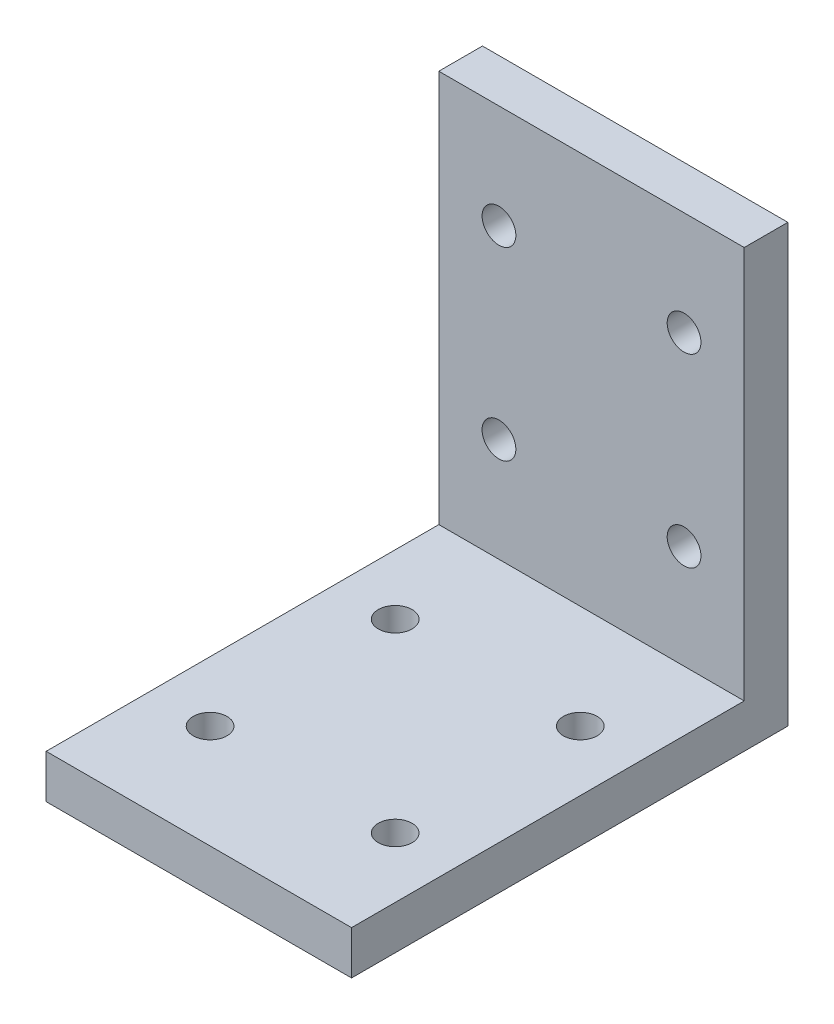
SolidWorks part; units mm, degrees
ref_plane "Front Plane" through (0, 0, 0) normal (0, 0, 1) x (1, 0, 0)
ref_plane "Top Plane" through (0, 0, 0) normal (0, 1, 0) x (1, 0, 0)
ref_plane "Right Plane" through (0, 0, 0) normal (1, 0, 0) x (0, 0, -1)
sketch "Sketch1" plane through (0, 0, 0) normal (1, 0, 0) x (0, 0, -1)
  line L0 (0, 0) -> (63.5, 0)
  line L1 (63.5, 0) -> (63.5, 63.5)
  line L2 (63.5, 63.5) -> (57.15, 63.5)
  line L3 (57.15, 63.5) -> (57.15, 6.35)
  line L4 (57.15, 6.35) -> (0, 6.35)
  line L5 (0, 6.35) -> (0, 0)
  dimension "D1" = 63.5
  dimension "D2" = 6.35
  dimension "D3" = 6.35
extrude "Boss-Extrude1" add sketch "Sketch1" against normal mid plane 44.45
hole_wizard "#10 (0.1935) Diameter Hole1" positions "Sketch4" profile "Sketch3" hole size "#10" standard "ANSI Inch" end condition up to next
sketch "Sketch4" plane through (0, 6.35, 0) normal (0, 1, 0) x (1, 0, 0)
  line L1 (-13.4704, 42.0454) -> (13.4704, 42.0454) construction
  line L2 (-13.4704, 42.0454) -> (-13.4704, 15.1046) construction
  line L3 (-13.4704, 15.1046) -> (13.4704, 15.1046) construction
  line L4 (13.4704, 42.0454) -> (13.4704, 15.1046) construction
  line L5 (-13.4704, 42.0454) -> (13.4704, 15.1046) construction
  line L6 (-13.4704, 15.1046) -> (13.4704, 42.0454) construction
  line L7 (22.225, 57.15) -> (22.225, 0) construction
  line L9 (-22.225, 28.575) -> (22.225, 28.575) construction
  line L10 (-22.225, 57.15) -> (-22.225, 0) construction
  point P2 (13.4704, 15.1046)
  point P73 (-13.4704, 42.0454)
  point P74 (-13.4704, 15.1046)
  point P75 (13.4704, 42.0454)
  point P85 (0, 28.575)
  point P92 (0, 28.575)
  dimension "D1" = 38.1
sketch "Sketch3" plane through (13.4704, 6.35, -15.1046) normal (1, 0, 0) x (0, 0, 1)
  line L0 (0, 0) -> (0, 6.351)
  line L1 (0, 6.351) -> (2.4574, 6.351)
  line L2 (2.4574, 6.351) -> (2.4574, 0)
  line L5 (2.4574, 0) -> (0, 0)
  line L11 (0, -6.35) -> (0, 107.95) construction
  dimension "Thru Hole Dia." = 4.9149
  dimension "Thru Hole Depth" = 6.351
ref_plane "Plane1" through (0, 31.75, -31.75) normal (0, 0.7071, -0.7071) x (-1, 0, 0)
mirror "Mirror1" about plane through (0, 31.75, -31.75) normal (0, 0.7071, -0.7071) of "#10 (0.1935) Diameter Hole1"
